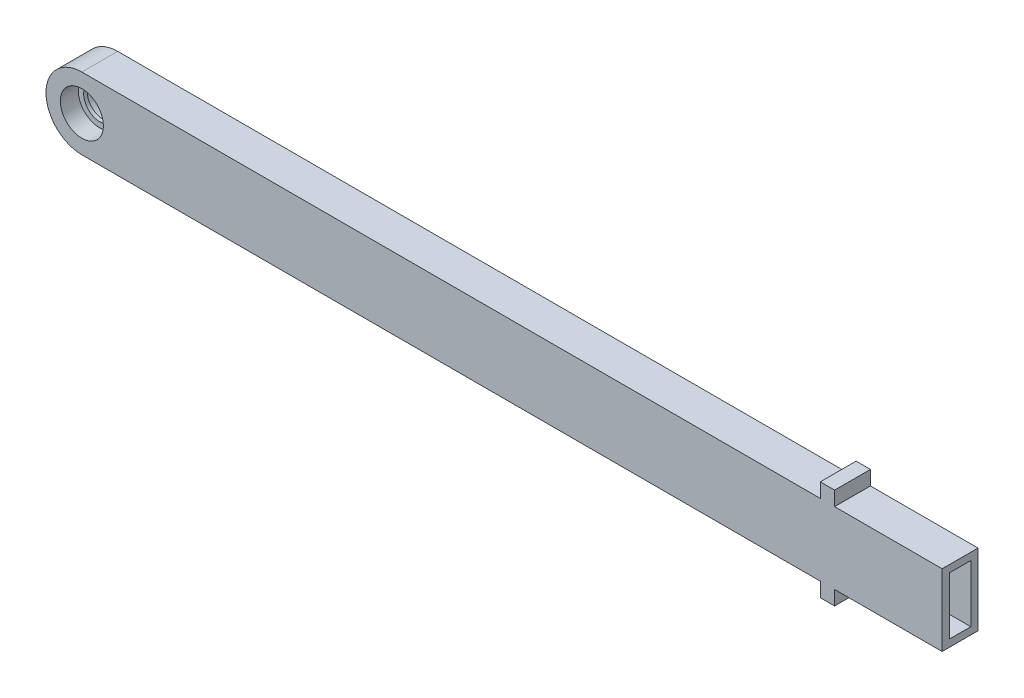
SolidWorks part; units mm, degrees
ref_plane "Front Plane" through (0, 0, 0) normal (0, 0, 1) x (1, 0, 0)
ref_plane "Top Plane" through (0, 0, 0) normal (0, 1, 0) x (1, 0, 0)
ref_plane "Right Plane" through (0, 0, 0) normal (1, 0, 0) x (0, 0, -1)
sketch "Sketch1" plane through (0, 0, 0) normal (0, 0, 1) x (1, 0, 0)
  line L0 (0, 0) -> (120, 0) construction
  line L1 (120, 5) -> (120, -5)
  line L2 (0, 5) -> (120, 5)
  line L3 (0, -5) -> (120, -5)
  circle A0 centre (0, 0) radius 3
  circle A1 centre (1.2272, 0) radius 0.1309
  arc A2 (0, 5) -> (0, -5) centre (0, 0) ccw
  dimension "D1" = 6
  dimension "D2" = 120
  dimension "D3" = 10
extrude "Boss-Extrude1" add sketch "Sketch1" along normal blind 5 contours L2 A2 L3 A0 region at (59.3864, 0, 0)
sketch "Sketch2" plane through (80, 0, 0) normal (1, 0, 0) x (0, 0, -1)
  line L0 (-5, 5) -> (0, 5) construction
  line L1 (-4, 4) -> (-1, 4)
  line L2 (-4, 4) -> (-4, -4)
  line L3 (-4, -4) -> (-1, -4)
  line L4 (-1, 4) -> (-1, -4)
  line L5 (-5, 5) -> (-5, -5) construction
  line L6 (0, 5) -> (0, -5) construction
  line L7 (-5, -5) -> (0, -5) construction
  dimension "D1" = 1
  dimension "D2" = 1
  dimension "D3" = 1
  dimension "D4" = 1
extrude "Cut-Extrude1" cut sketch "Sketch2" against normal blind 10 from surface starting at face at (120, 0, 2.5)
sketch "Sketch3" plane through (0, 0, 0) normal (0, 0, -1) x (-1, 0, 0)
  line L0 (0, 0) -> (-22, 0) construction
  line L3 (-22, 2) -> (0, 3)
  line L4 (-22, -2) -> (0, -3)
  arc A4 (0, -3) -> (0, 3) centre (0, 0) ccw
  arc A5 (-22, 2) -> (-22, -2) centre (-22, 0) ccw
  dimension "D2" = 6
  dimension "D3" = 4
  dimension "D1" = 22
extrude "Cut-Extrude2" cut sketch "Sketch3" against normal blind 2
sketch "Sketch4" plane through (0, 0, 2) normal (0, 0, -1) x (-1, 0, 0)
  circle A1 centre (0, 0) radius 2.25
  circle A2 centre (0, 0) radius 3
  dimension "D1" = 4.5
  dimension "D2" = 6
extrude "Boss-Extrude2" add sketch "Sketch4" against normal blind 0.5
sketch "Sketch5" plane through (0, 5, 0) normal (0, 1, 0) x (1, 0, 0)
  line L0 (105, 0) -> (105, -5)
  line L1 (0, 0) -> (120, 0) construction
  line L2 (0, -5) -> (120, -5) construction
  line L4 (103, 0) -> (103, -5)
  line L5 (103, -5) -> (105, -5)
  line L6 (103, 0) -> (105, 0)
  line L7 (120, -5) -> (120, 0) construction
  dimension "D1" = 15
  dimension "D2" = 2
extrude "Boss-Extrude3" add sketch "Sketch5" along normal blind 2
extrude "Boss-Extrude4" add sketch "Sketch5<2>" against normal blind 12
sketch "Sketch5<2>" plane through (0, 5, 0) normal (0, 1, 0) x (1, 0, 0) same geometry as "Sketch5"
